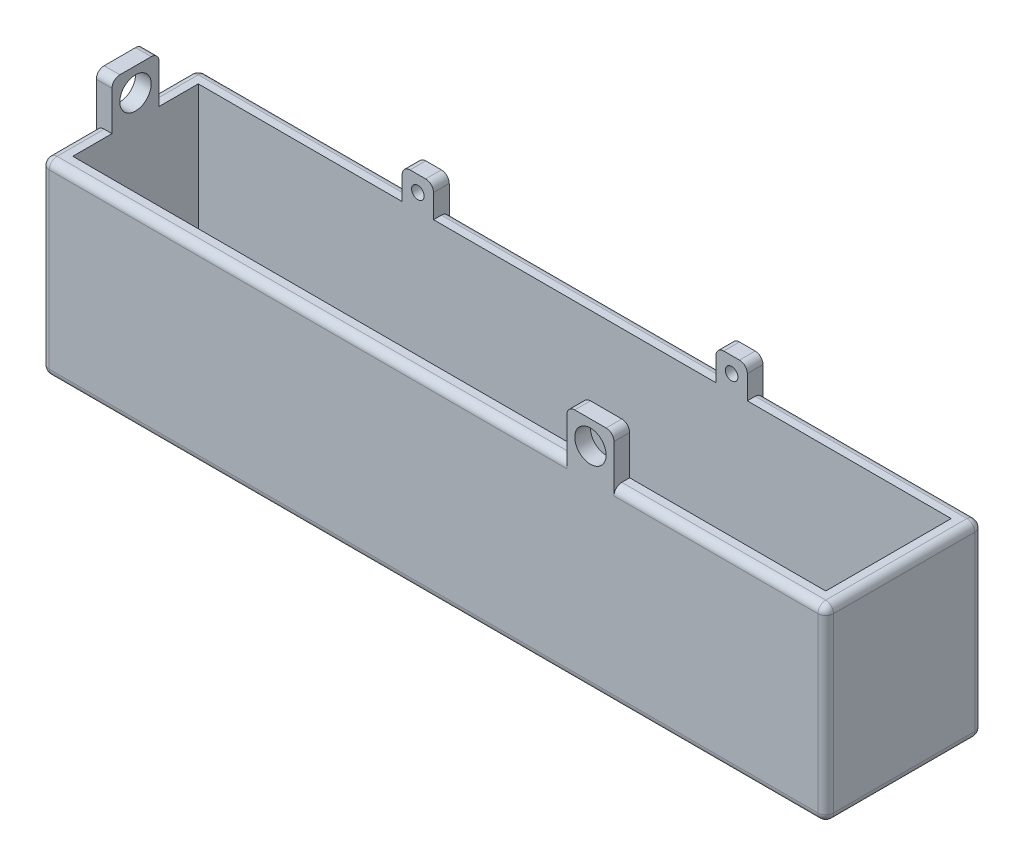
SolidWorks part; units mm, degrees
ref_plane "Front Plane" through (0, 0, 0) normal (0, 0, 1) x (1, 0, 0)
ref_plane "Top Plane" through (0, 0, 0) normal (0, 1, 0) x (1, 0, 0)
ref_plane "Right Plane" through (0, 0, 0) normal (1, 0, 0) x (0, 0, -1)
sketch "Sketch1" plane through (0, 0, 0) normal (0, 0, 1) x (1, 0, 0)
  line L0 (-120, -25) -> (-125, -25) construction
  line L1 (-125, -30) -> (125, -30)
  line L2 (-125, -30) -> (-125, 30)
  line L3 (-125, 30) -> (125, 30)
  line L4 (125, -30) -> (125, 30)
  line L5 (-125, -30) -> (125, 30) construction
  line L6 (-125, 30) -> (125, -30) construction
  line L7 (-120, -25) -> (120, -25)
  line L8 (-120, -25) -> (-120, 25)
  line L9 (-120, 25) -> (120, 25)
  line L10 (120, -25) -> (120, 25)
  line L11 (-120, -25) -> (120, 25) construction
  line L12 (-120, 25) -> (120, -25) construction
  line L13 (-55, 30) -> (-45, 30)
  line L14 (-55, 30) -> (-55, 40)
  line L15 (-55, 40) -> (-45, 40)
  line L16 (-45, 30) -> (-45, 40)
  line L21 (-120, -25) -> (-120, -30) construction
  line L22 (0, -1000) -> (0, 49000) construction
  line L23 (45, 30) -> (45, 40)
  line L24 (55, 40) -> (45, 40)
  line L25 (55, 30) -> (55, 40)
  line L26 (55, 30) -> (45, 30)
  line L27 (-120, 25) -> (-120, 30)
  line L28 (120, 25) -> (120, 30)
  line L30 (57.5, 30) -> (42.5, 30)
  line L31 (57.5, 30) -> (57.5, 45)
  line L32 (57.5, 45) -> (42.5, 45)
  line L33 (42.5, 30) -> (42.5, 45)
  circle A0 centre (-50, 35) radius 2
  circle A1 centre (50, 35) radius 2
  circle A2 centre (50, 37.5) radius 5
  point P0 (0, 0)
  point P6 (0, 0)
  point P18 (-50, 40)
  point P19 (-55, 35)
  point P33 (57.5, 37.5)
  point P40 (50, 45)
  dimension "D6" = 4
  dimension "D7" = 10
  dimension "D1" = 240
  dimension "D2" = 50
  dimension "D3" = 100
  dimension "D4" = 5
  dimension "D5" = 10
  dimension "D8" = 15
extrude "Boss-Extrude1" add sketch "Sketch1" along normal mid plane 50 contours L28 L10 L7 L8 L27 L3 L2 L1 L4 | L7 L10 L9 L8 | L9 L28 L3 L27 region at (-122.429, 0, 0) region at (0, 27.5, 0) region at (0, 0, 0)
extrude "Cut-Extrude1" cut sketch "Sketch1<5>" against normal mid plane 40 contours L7 L10 L9 L8 | L9 L28 L3 L27 region at (0, 27.5, 0) region at (0, 0, 0)
sketch "Sketch1<5>" plane through (0, 0, 0) normal (0, 0, 1) x (1, 0, 0) same geometry as "Sketch1"
extrude "Boss-Extrude3" add sketch "Sketch1<6>" along normal up to surface (-20 mm away) from surface contours L3 L16 L15 L14 A0 | L3 L25 L24 L23 A1 | A2 L24 A1 | A2 L25 L24 | A2 L24 L23 region at (-54.8586, 35, 0) region at (50, 31.9608, 0) region at (54.8016, 39.3837, 0) region at (50, 37.0513, 0) region at (45.1984, 39.3837, 0) up to face at (0, 2.5, -20) starting at face at (0, 0, -25)
sketch "Sketch1<6>" plane through (0, 0, 0) normal (0, 0, 1) x (1, 0, 0) same geometry as "Sketch1"
extrude "Boss-Extrude4" add sketch "Sketch1<8>" against normal up to surface (-20 mm away) from surface contours A2 L23 L3 L25 | A2 L24 L25 L3 L31 L32 L33 L23 | A2 L24 L23 | A2 L25 L24 region at (56.25, 30.2121, 0) region at (50, 31.9608, 0) region at (54.8016, 39.3837, 0) region at (45.1984, 39.3837, 0) up to face at (0, 2.5, 20) starting at face at (0, 0, 25)
sketch "Sketch1<8>" plane through (0, 0, 0) normal (0, 0, 1) x (1, 0, 0) same geometry as "Sketch1"
sketch "Sketch2" plane through (-125, 0, 0) normal (-1, 0, 0) x (0, 0, 1)
  line L0 (25, 30) -> (-25, 30) construction
  line L1 (-7.5, 30) -> (7.5, 30)
  line L2 (-7.5, 30) -> (-7.5, 45)
  line L3 (-7.5, 45) -> (7.5, 45)
  line L4 (7.5, 30) -> (7.5, 45)
  line L5 (20, 30) -> (20, 45) construction
  circle A0 centre (0, 37.5) radius 5
  point P6 (0, 30)
  point P9 (0, 45)
  point P16 (7.5, 37.5)
  line M7 (25, 30) -> (-25, 30)
  dimension "D1" = 10
extrude "Boss-Extrude5" add sketch "Sketch2" along direction (1, 0, 0) on the side against the normal up to surface (5 mm away) contours L4 L3 L2 A0 M7 region at (-125, 37.5, -7.2879) up to face at (-120, 2.5, 0)
fillet "Fillet1" radius 2.5 24 edges at (125, 0, 25) (-125, 30, 16.25) (-125, 30, -16.25) (-125, -30, 0) (-55, 40, -22.5) (-45, 40, -22.5) (-122.5, 45, 7.5) (-122.5, 45, -7.5) (57.5, 45, 22.5) (42.5, 45, 22.5) (45, 40, -22.5) (55, 40, -22.5) (90, 30, -25) (0, 30, -25) (-90, 30, -25) (-125, 0, -25) (0, -30, -25) (125, -30, 0) (125, 30, 0) (125, 0, -25) (-125, 0, 25) (0, -30, 25) (91.25, 30, 25) (-41.25, 30, 25)
